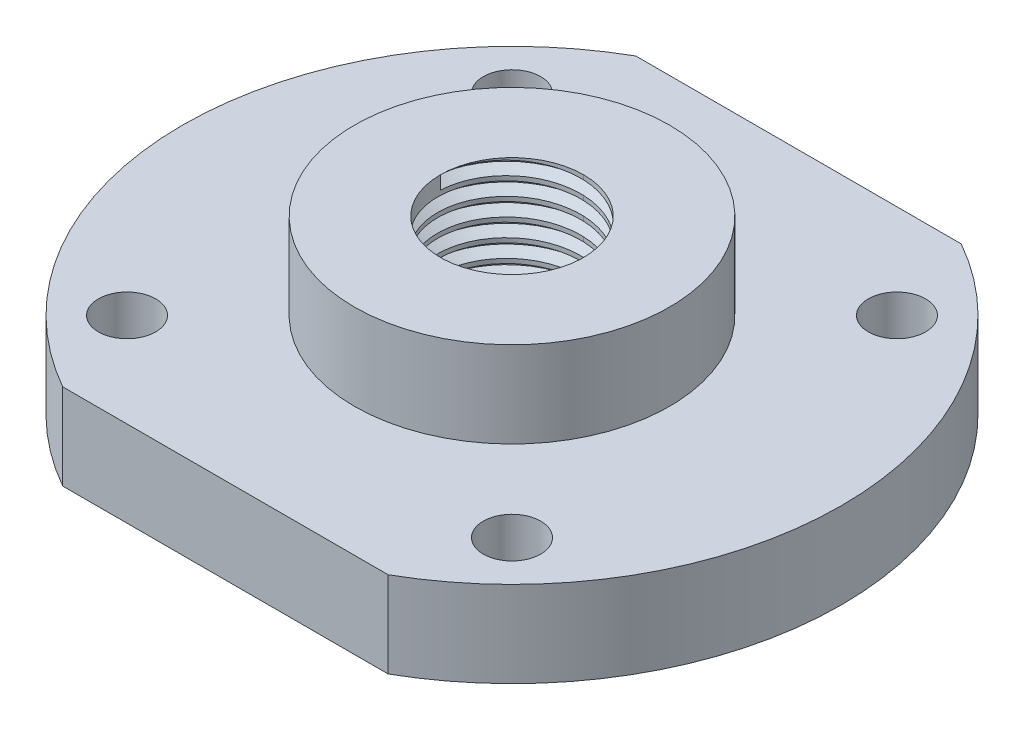
SolidWorks part; units mm, degrees
material "6061 Alloy"
ref_plane "Front Plane" through (0, 0, 0) normal (0, 0, 1) x (1, 0, 0)
ref_plane "Top Plane" through (0, 0, 0) normal (0, 1, 0) x (1, 0, 0)
ref_plane "Right Plane" through (0, 0, 0) normal (1, 0, 0) x (0, 0, -1)
sketch "Sketch2" plane through (0, 0, 0) normal (0, 1, 0) x (1, 0, 0)
  line L0 (0, 0) -> (0, 20)
  line L1 (0, 0) -> (0, -20)
  line L2 (0, 20) -> (11.3578, 20)
  line L3 (0, 20) -> (-11.3578, 20)
  line L4 (0, -20) -> (-11.3578, -20)
  line L5 (0, -20) -> (11.3578, -20)
  line L6 (0, 0) -> (13.435, 13.435)
  line L7 (13.435, 13.435) -> (-13.435, -13.435)
  line L9 (-13.435, -13.435) -> (13.435, -13.435)
  line L10 (-13.435, -13.435) -> (-13.435, 13.435)
  line L11 (-13.435, 13.435) -> (13.435, 13.435)
  line L12 (13.435, -13.435) -> (13.435, 13.435)
  circle A0 centre (0, 0) radius 23
  circle A1 centre (0, 0) radius 5
  circle A2 centre (0, 0) radius 19
  circle A3 centre (-13.435, 13.435) radius 2
  circle A4 centre (13.435, 13.435) radius 2
  circle A5 centre (13.435, -13.435) radius 2
  circle A6 centre (-13.435, -13.435) radius 2
  dimension "D1" = 46
  dimension "D2" = 20
  dimension "D3" = 20
extrude "Boss-Extrude1" add sketch "Sketch2" along normal blind 6 contours A6 A2 A3 L0 L3 A0 L4 L1 | A3 L11 L0 A2 | A6 L10 A3 A2 | A6 L7 A1 L0 L11 A3 L10 | A6 L9 L1 A1 L7 | A5 L12 A4 L7 A1 L1 L9 | A5 L9 L1 A2 | A6 A2 L1 L9 | A4 A2 L0 L11 | A4 L11 L0 A1 L7 | A5 A2 A4 L12 | A5 A2 L1 L5 A0 L2 L0 A4 region at (-7.9881, 0, -3.2063) region at (4.7266, 0, -9.6188) region at (7.9881, 0, 3.2063) region at (-4.7266, 0, 9.6188) region at (-4.9412, 0, -15.7451) region at (4.9412, 0, -15.7451) region at (4.9412, 0, 15.7451) region at (-4.9412, 0, 15.7451) region at (-6.4909, 0, -18.3471) region at (0.4614, 0, -19.5) region at (15.7451, 0, 0) region at (-15.7451, 0, 0)
sketch "Sketch3" plane through (0, 0, 0) normal (0, -1, 0) x (1, 0, 0)
  circle A0 centre (0, 0) radius 15
  circle A1 centre (0, 0) radius 5
extrude "Boss-Extrude2" add sketch "Sketch3" along normal blind 2
sketch "Sketch4" plane through (0, 6, 0) normal (0, 1, 0) x (1, 0, 0)
  circle A0 centre (0, 0) radius 5
  circle A1 centre (0, 0) radius 11
extrude "Boss-Extrude3" add sketch "Sketch4" along normal blind 6
thread "Thread1" pitch 1.25 method cut profile "Thread Profile1" start angle 0, offset 0, length 10, pitch 1.25, diameter 10
ref_plane "Plane1" through (-5, 12, 0) normal (0, 0, 1) x (-1, 0, 0)
sketch "Thread Profile1" plane through (-5, 12, 0) normal (0, 0, 1) x (-1, 0, 0)
  line L0 (0, 0) -> (0, 1.25) construction
  line L1 (0, 0) -> (0.6766, 0.3906)
  line L2 (0.6766, 0.3906) -> (0.6766, 0.5469)
  line L3 (0.6766, 0.5469) -> (0, 0.9375)
  line L4 (0.6766, 0.4687) -> (0, 0.4687) construction
  line L11 (0, 0) -> (0, 0.9375)
  point P2 (0, 0)
  dimension "Pitch" = 1.25
  dimension "Profile_Angle" = 60
  dimension "Profile_Land" = 0.1562
  dimension "Profile_Height" = 0.6766
